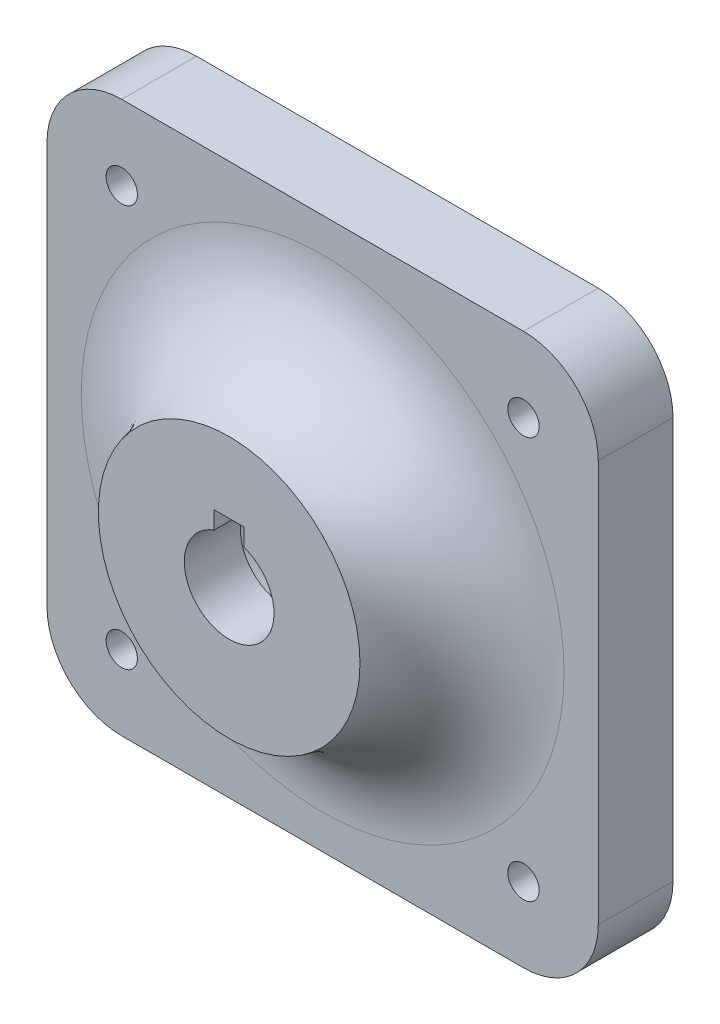
SolidWorks part; units mm, degrees
ref_plane "Front Plane" through (0, 0, 0) normal (0, 0, 1) x (1, 0, 0)
ref_plane "Top Plane" through (0, 0, 0) normal (0, 1, 0) x (1, 0, 0)
ref_plane "Right Plane" through (0, 0, 0) normal (1, 0, 0) x (0, 0, -1)
sketch "Spacing" plane through (0, 0, 0) normal (0, 0, 1) x (1, 0, 0)
  line L1 (-26.8701, -26.8701) -> (26.8701, -26.8701)
  line L2 (-26.8701, -26.8701) -> (-26.8701, 26.8701)
  line L3 (-26.8701, 26.8701) -> (26.8701, 26.8701)
  line L4 (26.8701, -26.8701) -> (26.8701, 26.8701)
  line L5 (-26.8701, -26.8701) -> (26.8701, 26.8701) construction
  line L6 (-26.8701, 26.8701) -> (26.8701, -26.8701) construction
  point P0 (0, 0)
  dimension "D1" = 76
sketch "Sketch1" plane through (0, 0, 7) normal (0, 0, 1) x (1, 0, 0)
  line L0 (36.8701, -26.8701) -> (36.8701, 26.8701)
  line L1 (26.8701, 36.8701) -> (-26.8701, 36.8701)
  line L2 (-36.8701, 26.8701) -> (-36.8701, -26.8701)
  line L3 (26.8701, -36.8701) -> (-26.8701, -36.8701)
  arc A0 (26.8701, -36.8701) -> (36.8701, -26.8701) centre (26.8701, -26.8701) ccw
  arc A1 (-36.8701, -26.8701) -> (-26.8701, -36.8701) centre (-26.8701, -26.8701) ccw
  arc A2 (-26.8701, 36.8701) -> (-36.8701, 26.8701) centre (-26.8701, 26.8701) ccw
  arc A3 (36.8701, 26.8701) -> (26.8701, 36.8701) centre (26.8701, 26.8701) ccw
  circle A6 centre (26.8701, -26.8701) radius 2.1
  circle A7 centre (-26.8701, -26.8701) radius 2.1
  circle A8 centre (-26.8701, 26.8701) radius 2.1
  circle A9 centre (26.8701, 26.8701) radius 2.1
  dimension "D1" = 20
  dimension "D2" = 4.2
extrude "Boss-Extrude1" add sketch "Sketch1" along normal blind 10 from offset 2
sketch "Sketch7" plane through (0, 0, 9) normal (0, 0, -1) x (-1, 0, 0)
  circle A0 centre (26.8701, -26.8701) radius 2.1 construction
  circle A1 centre (26.8701, -26.8701) radius 2.1
  circle A2 centre (26.8701, -26.8701) radius 3.6
  circle A3 centre (-26.8701, -26.8701) radius 3.6
  circle A4 centre (-26.8701, -26.8701) radius 2.1
  circle A5 centre (-26.8701, 26.8701) radius 3.6
  circle A6 centre (-26.8701, 26.8701) radius 2.1
  circle A7 centre (26.8701, 26.8701) radius 3.6
  circle A8 centre (26.8701, 26.8701) radius 2.1
  point P4 (14.9615, -15.803)
  point P6 (-19.3685, 23.6651)
  point P15 (-26.8701, 26.8701)
  point P17 (26.8701, 26.8701)
  dimension "D1" = 7.2
  dimension "D2" = 2
  dimension "D3" = 2
extrude "Boss-Extrude3" add sketch "Sketch7" along normal up to surface (2 mm away)
sketch "Sketch3" plane through (0, 0, 19) normal (0, 0, 1) x (1, 0, 0)
  circle A0 centre (0, 0) radius 17.5
  dimension "D1" = 35
extrude "Boss-Extrude2" add sketch "Sketch3" along normal blind 12.5
sketch "Sketch2" plane through (0, 0, 9) normal (0, 0, -1) x (-1, 0, 0)
  circle A0 centre (0, 0) radius 15
  dimension "D1" = 30
extrude "Cut-Extrude1" cut sketch "Sketch2" against normal blind 15
fillet "Fillet1" radius 15 1 edges at (17.5, 0, 19)
sketch "Sketch4" plane through (0, 0, 31.5) normal (0, 0, 1) x (1, 0, 0)
  circle A0 centre (0, 0) radius 6
  dimension "D1" = 12
extrude "Cut-Extrude2" cut sketch "Sketch4" against normal through all
sketch "Sketch5" plane through (0, 0, 31.5) normal (0, 0, 1) x (1, 0, 0)
  line L1 (2, 8) -> (-2, 8)
  line L2 (2, 8) -> (2, 5.6569)
  line L3 (2, 5.6569) -> (-2, 5.6569)
  line L4 (-2, 8) -> (-2, 5.6569)
  line L5 (2, 8) -> (-2, 5.6569) construction
  line L6 (2, 5.6569) -> (-2, 8) construction
  circle A0 centre (0, 0) radius 6 construction
  point P0 (0, 6.8284)
  dimension "D1" = 4
  dimension "D2" = 2
extrude "Cut-Extrude3" cut sketch "Sketch5" against normal through all
